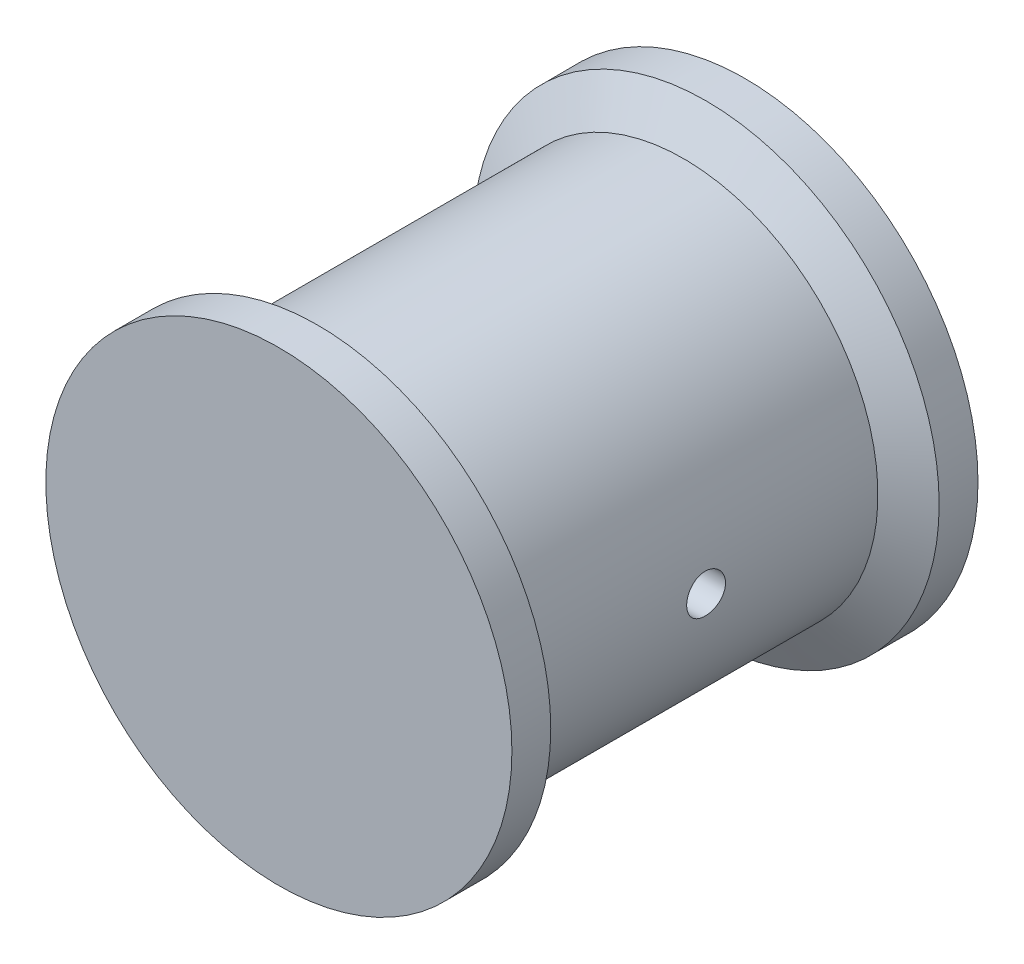
SolidWorks part; units mm, degrees
ref_plane "Front Plane" through (0, 0, 0) normal (0, 0, 1) x (1, 0, 0)
ref_plane "Top Plane" through (0, 0, 0) normal (0, 1, 0) x (1, 0, 0)
ref_plane "Right Plane" through (0, 0, 0) normal (1, 0, 0) x (0, 0, -1)
sketch "Sketch2" plane through (0, 0, 0) normal (0, 0, 1) x (1, 0, 0)
  line L0 (-1.4142, 2.3) -> (1.4142, 2.3)
  line L1 (0, 0) -> (0, -2.7) construction
  circle A0 centre (0, 0) radius 2.7
  circle A1 centre (0, 0) radius 10
  dimension "D1" = 5.4
  dimension "D2" = 20
  dimension "D3" = 5
extrude "Boss-Extrude1" add sketch "Sketch2" along normal blind 10 contours A1 A0 | L0 A0 region at (0, 2.4611, 0) region at (-9.7172, 0, 0)
sketch "Sketch3" plane through (0, 0, 10) normal (0, 0, 1) x (1, 0, 0)
  circle A0 centre (0, 0) radius 25
  dimension "D1" = 50
extrude "Boss-Extrude2" add sketch "Sketch3" along normal blind 60
sketch "Sketch4" plane through (0, 0, 70) normal (0, 0, 1) x (1, 0, 0)
  circle A0 centre (0, 0) radius 30
  circle A1 centre (0, 0) radius 25 construction
  dimension "D1" = 5
extrude "Boss-Extrude3" add sketch "Sketch4" against normal blind 5
ref_plane "Plane1" through (0, 0, 40) normal (0, 0, 1) x (1, 0, 0)
mirror "Mirror1" about plane through (0, 0, 40) normal (0, 0, 1) of "Boss-Extrude3"
chamfer "Chamfer1" distance 5 angle 30 2 edges at (25, 0, 65) (-25, 0, 15) first distance on face at (25, 0, 65) first distance on face at (-25, 0, 15)
sketch "Sketch5" plane through (0, 0, 0) normal (1, 0, 0) x (0, 0, -1)
  line L0 (-17.8868, 0) -> (-62.1132, 0) construction
  line L1 (-17.8868, -25) -> (-17.8868, 25) construction
  line L2 (-62.1132, -25) -> (-62.1132, 25) construction
  circle A0 centre (-40, 0) radius 2.5
  dimension "D1" = 5
extrude "Cut-Extrude1" cut sketch "Sketch5" against normal through all both and the other way through all
sketch "Sketch6" plane through (0, 0, 10) normal (0, 0, -1) x (-1, 0, 0)
  line L1 (1.4142, 2.3) -> (-1.4142, 2.3)
  line L2 (1.4142, 2.3) -> (-1.4142, 2.3)
  arc A1 (-1.4142, 2.3) -> (1.4142, 2.3) centre (0, 0) ccw
  arc A2 (-1.4142, 2.3) -> (1.4142, 2.3) centre (0, 0) ccw
  dimension "D1" = 0
extrude "Cut-Extrude2" cut sketch "Sketch6" against normal blind 20
